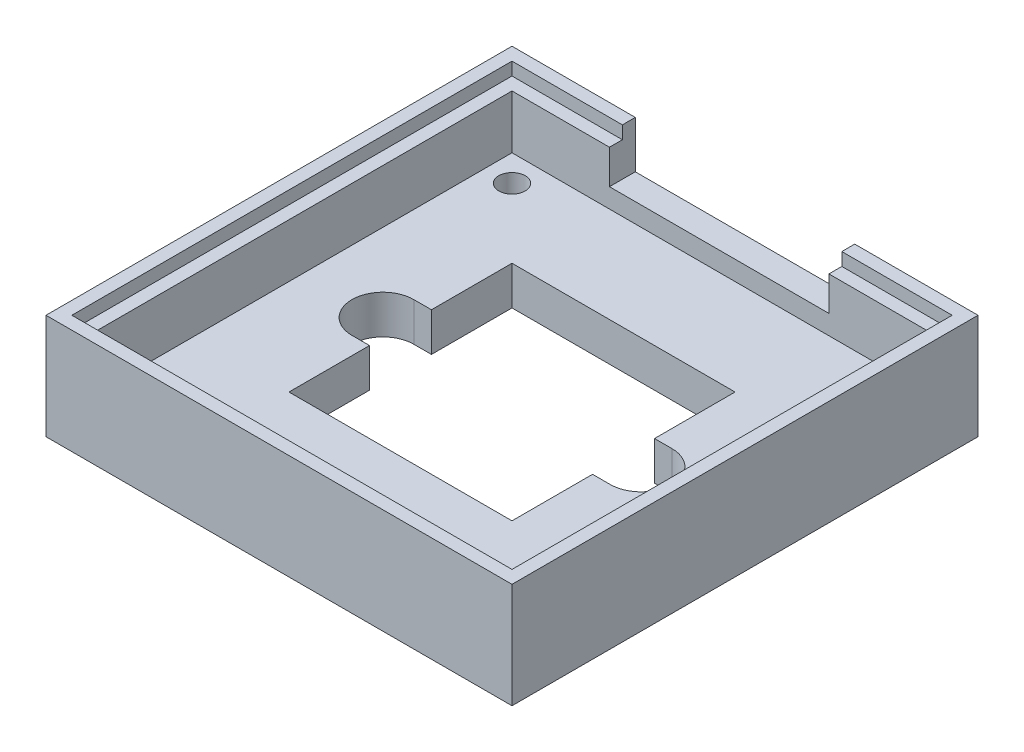
SolidWorks part; units mm, degrees
ref_plane "Front Plane" through (0, 0, 0) normal (0, 0, 1) x (1, 0, 0)
ref_plane "Top Plane" through (0, 0, 0) normal (0, 1, 0) x (1, 0, 0)
ref_plane "Right Plane" through (0, 0, 0) normal (1, 0, 0) x (0, 0, -1)
sketch "Sketch1" plane through (0, 0, 0) normal (0, 1, 0) x (1, 0, 0)
  line L0 (-10, 2.3) -> (-8.54, 2.3)
  line L1 (-16.05, -16.05) -> (16.05, -16.05)
  line L2 (-16.05, -16.05) -> (-16.05, 16.05)
  line L3 (-16.05, 16.05) -> (16.05, 16.05)
  line L4 (16.05, -16.05) -> (16.05, 16.05)
  line L5 (-16.05, -16.05) -> (16.05, 16.05) construction
  line L6 (-16.05, 16.05) -> (16.05, -16.05) construction
  line L7 (-8.54, -8.54) -> (8.54, -8.54)
  line L8 (-8.54, -8.54) -> (-8.54, -2.3)
  line L9 (-8.54, 8.54) -> (8.54, 8.54)
  line L10 (8.54, -8.54) -> (8.54, -2.3)
  line L11 (-8.54, -8.54) -> (8.54, 8.54) construction
  line L12 (-8.54, 8.54) -> (8.54, -8.54) construction
  line L13 (-10, -2.3) -> (-8.54, -2.3)
  line L14 (-8.54, 2.3) -> (-8.54, 8.54)
  line L15 (0, -8.54) -> (0, 8.54) construction
  line L16 (10, -2.3) -> (8.54, -2.3)
  line L17 (10, 2.3) -> (8.54, 2.3)
  line L18 (8.54, 2.3) -> (8.54, 8.54)
  line L19 (-8.64, 2.4) -> (-8.64, 8.64)
  line L20 (-8.64, 8.64) -> (8.64, 8.64)
  line L21 (8.64, 2.4) -> (8.64, 8.64)
  line L22 (10, 2.4) -> (8.64, 2.4)
  line L23 (10, -2.4) -> (8.64, -2.4)
  line L24 (8.64, -8.64) -> (8.64, -2.4)
  line L25 (-8.64, -8.64) -> (8.64, -8.64)
  line L26 (-8.64, -8.64) -> (-8.64, -2.4)
  line L27 (-10, -2.4) -> (-8.64, -2.4)
  line L28 (-10, 2.4) -> (-8.64, 2.4)
  line L33 (-18.05, -18.05) -> (-18.05, 18.05)
  line L34 (-18.05, 18.05) -> (18.05, 18.05)
  line L35 (18.05, -18.05) -> (18.05, 18.05)
  line L36 (-18.05, -18.05) -> (18.05, -18.05)
  circle A0 centre (-14, 14) radius 1.025
  circle A1 centre (14, 14) radius 1.025
  circle A2 centre (14, -14) radius 1.025
  circle A3 centre (-14, -14) radius 1.025
  circle A4 centre (-10, 0) radius 1
  circle A5 centre (10, 0) radius 1
  arc A6 (-10, 2.3) -> (-10, -2.3) centre (-10, 0) ccw
  arc A7 (10, 2.3) -> (10, -2.3) centre (10, 0) cw
  arc A8 (10, 2.4) -> (10, -2.4) centre (10, 0) cw
  arc A9 (-10, 2.4) -> (-10, -2.4) centre (-10, 0) ccw
  point P0 (0, 0)
  point P9 (0, 0)
  point P23 (-12.3, 0)
  dimension "D7" = 2
  dimension "D13" = 2.05
  dimension "D1" = 32.1
  dimension "D2" = 32.1
  dimension "D3" = 14
  dimension "D4" = 2
  dimension "D6" = 17.08
  dimension "D8" = 10
  dimension "D10" = 4.6
  dimension "D11" = 0.1
  dimension "D14" = 2
  dimension "D5" = 2
  dimension "D9" = 2
extrude "Boss-Extrude1" add sketch "Sketch1" along normal blind 3 contours L4 L1 L2 L3 | L1 L4 L3 L2 A9 L28 L19 L20 L21 L22 A8 L23 L24 L25 L26 L27 A0 A1 A2 A3 region at (-15.596, 0, 0) region at (-17.5395, 0, 0)
extrude "Boss-Extrude2" add sketch "Sketch1<3>" along normal blind 8.15 contours L33 L36 L35 L34 L4 L1 L2 L3
sketch "Sketch1<3>" plane through (0, 0, 0) normal (0, 1, 0) x (1, 0, 0) same geometry as "Sketch1"
sketch "Sketch2" plane through (0, 0, -18.05) normal (0, 0, -1) x (-1, 0, 0)
  line L1 (-8.5, 8.15) -> (8.5, 8.15)
  line L2 (-8.5, 8.15) -> (-8.5, 4.5)
  line L3 (-8.5, 4.5) -> (8.5, 4.5)
  line L4 (8.5, 8.15) -> (8.5, 4.5)
  line L6 (18.05, 0) -> (-18.05, 0) construction
  line L7 (18.05, 8.15) -> (-18.05, 8.15) construction
  point P6 (0, 4.5)
  dimension "D1" = 17
  dimension "D2" = 4.5
extrude "Cut-Extrude1" cut sketch "Sketch2" against normal blind 6
sketch "Sketch4" plane through (0, 8.15, 0) normal (0, 1, 0) x (1, 0, 0)
  line L27 (-16.05, -16.05) -> (16.05, -16.05) construction
  line L28 (16.05, -16.05) -> (16.05, 16.05) construction
  line L29 (8.5, 16.05) -> (16.05, 16.05) construction
  line L30 (8.5, 16.05) -> (8.5, 18.05) construction
  line L31 (-8.5, 18.05) -> (-8.5, 16.05) construction
  line L32 (17.05, -17.05) -> (-17.05, -17.05)
  line L33 (17.05, 17.05) -> (17.05, -17.05)
  line L34 (8.5, 17.05) -> (17.05, 17.05)
  line L35 (-17.05, 17.05) -> (-8.5, 17.05)
  line L36 (-17.05, -17.05) -> (-17.05, 17.05)
  line L37 (17.05, -17.05) -> (-17.05, -17.05)
  line L38 (17.05, 17.05) -> (17.05, -17.05)
  line L39 (8.5, 17.05) -> (17.05, 17.05)
  line L40 (-17.05, 17.05) -> (-8.5, 17.05)
  line L41 (-17.05, -17.05) -> (-17.05, 17.05)
  line L42 (-16.05, 16.05) -> (-8.5, 16.05) construction
  line L43 (-16.05, -16.05) -> (-16.05, 16.05) construction
  line L44 (-16.05, -16.05) -> (16.05, -16.05)
  line L45 (16.05, -16.05) -> (16.05, 16.05)
  line L46 (8.5, 16.05) -> (16.05, 16.05)
  line L47 (8.5, 16.05) -> (8.5, 17.05)
  line L48 (-8.5, 17.05) -> (-8.5, 16.05)
  line L49 (-16.05, 16.05) -> (-8.5, 16.05)
  line L50 (-16.05, -16.05) -> (-16.05, 16.05)
  dimension "D1" = 1
extrude "Cut-Extrude2" cut sketch "Sketch4" against normal blind 1
